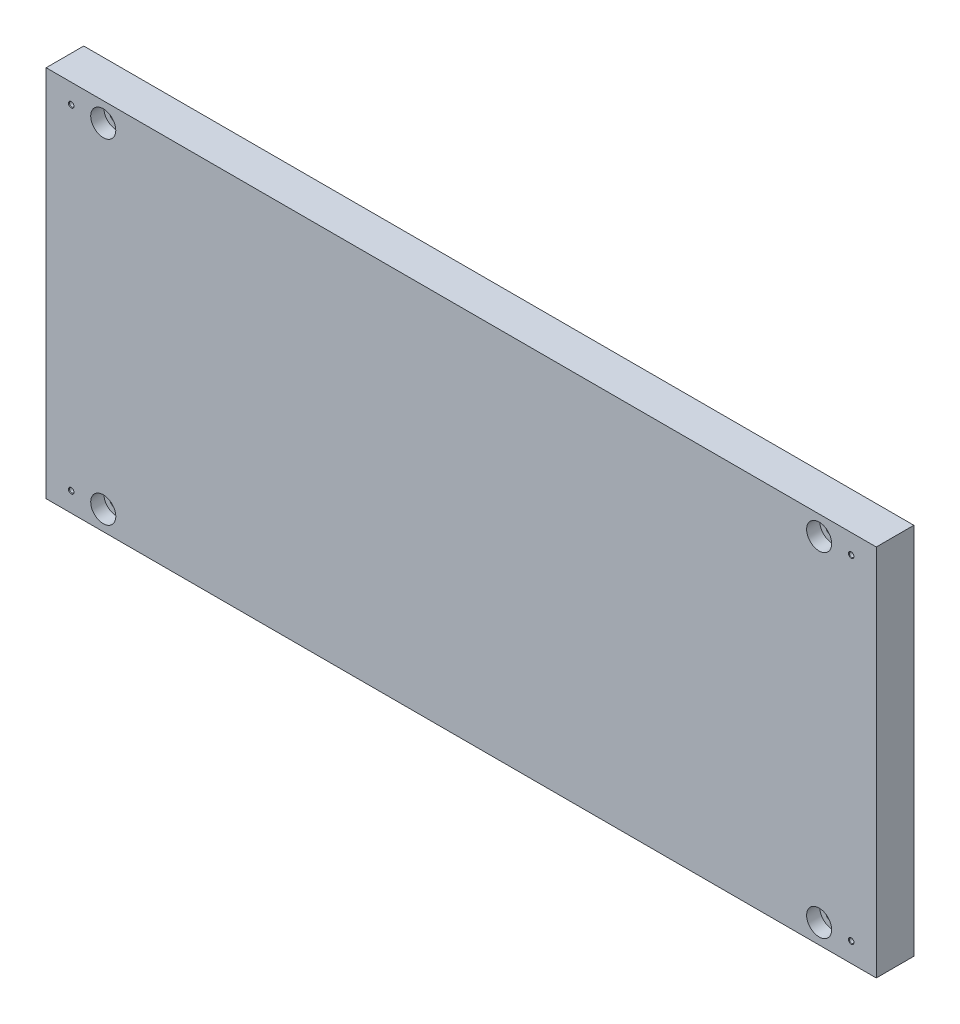
SolidWorks part; units mm, degrees
ref_plane "Płaszczyzna przednia" through (0, 0, 0) normal (0, 0, 1) x (1, 0, 0)
ref_plane "Płaszczyzna górna" through (0, 0, 0) normal (0, 1, 0) x (1, 0, 0)
ref_plane "Płaszczyzna prawa" through (0, 0, 0) normal (1, 0, 0) x (0, 0, -1)
sketch "Szkic1" plane through (0, 0, 0) normal (0, 0, 1) x (1, 0, 0)
  line L0 (-298, -134) -> (298, -134)
  line L1 (298, -134) -> (298, 134)
  line L2 (298, 134) -> (-298, 134)
  line L3 (-298, 134) -> (-298, -134)
extrude "Dodanie-wyciągnięcie1" add sketch "Szkic1" along normal blind 27
ref_plane "Płaszczyzna1" through (257, 0, 0) normal (1, 0, 0) x (0, 0, -1)
sketch "Szkic2" plane through (257, 0, 0) normal (1, 0, 0) x (0, 0, -1)
  line L0 (-17.5, 120) -> (-17.5, 125)
  line L1 (-17.5, 125) -> (0, 125)
  line L2 (0, 125) -> (0, 120)
  line L3 (0, 120) -> (-17.5, 120)
  line L4 (0, 120) -> (-17.5, 120) construction
revolve "Wycięcie-obrót1" cut sketch "Szkic2" angle 360 about L4 reverse direction yes
sketch "Szkic3" plane through (257, 0, 0) normal (1, 0, 0) x (0, 0, -1)
  line L0 (0, -120) -> (0, -125)
  line L1 (0, -125) -> (-17.5, -125)
  line L2 (-17.5, -125) -> (-17.5, -120)
  line L3 (-17.5, -120) -> (0, -120)
  line L4 (-17.5, -120) -> (0, -120) construction
revolve "Wycięcie-obrót2" cut sketch "Szkic3" angle 360 about L4 reverse direction yes
ref_plane "Płaszczyzna2" through (-257, 0, 0) normal (1, 0, 0) x (0, 0, -1)
sketch "Szkic4" plane through (-257, 0, 0) normal (1, 0, 0) x (0, 0, -1)
  line L0 (-17.5, 120) -> (-17.5, 125)
  line L1 (-17.5, 125) -> (0, 125)
  line L2 (0, 125) -> (0, 120)
  line L3 (0, 120) -> (-17.5, 120)
  line L4 (0, 120) -> (-17.5, 120) construction
revolve "Wycięcie-obrót3" cut sketch "Szkic4" angle 360 about L4 reverse direction yes
sketch "Szkic5" plane through (-257, 0, 0) normal (1, 0, 0) x (0, 0, -1)
  line L0 (0, -120) -> (0, -125)
  line L1 (0, -125) -> (-17.5, -125)
  line L2 (-17.5, -125) -> (-17.5, -120)
  line L3 (-17.5, -120) -> (0, -120)
  line L4 (-17.5, -120) -> (0, -120) construction
revolve "Wycięcie-obrót4" cut sketch "Szkic5" angle 360 about L4 reverse direction yes
sketch "Szkic6" plane through (-257, 0, 0) normal (1, 0, 0) x (0, 0, -1)
  line L0 (-27, 120) -> (-27, 129)
  line L1 (-27, 129) -> (-17.5, 129)
  line L2 (-17.5, 129) -> (-17.5, 120)
  line L3 (-17.5, 120) -> (-27, 120)
  line L4 (-17.5, 120) -> (-27, 120) construction
revolve "Wycięcie-obrót5" cut sketch "Szkic6" angle 360 about L4 reverse direction yes
sketch "Szkic7" plane through (257, 0, 0) normal (1, 0, 0) x (0, 0, -1)
  line L0 (-27, 120) -> (-27, 129)
  line L1 (-27, 129) -> (-17.5, 129)
  line L2 (-17.5, 129) -> (-17.5, 120)
  line L3 (-17.5, 120) -> (-27, 120)
  line L4 (-17.5, 120) -> (-27, 120) construction
revolve "Wycięcie-obrót6" cut sketch "Szkic7" angle 360 about L4 reverse direction yes
sketch "Szkic8" plane through (-257, 0, 0) normal (1, 0, 0) x (0, 0, -1)
  line L0 (-17.5, -120) -> (-17.5, -129)
  line L1 (-17.5, -129) -> (-27, -129)
  line L2 (-27, -129) -> (-27, -120)
  line L3 (-27, -120) -> (-17.5, -120)
  line L4 (-27, -120) -> (-17.5, -120) construction
revolve "Wycięcie-obrót7" cut sketch "Szkic8" angle 360 about L4 reverse direction yes
sketch "Szkic9" plane through (257, 0, 0) normal (1, 0, 0) x (0, 0, -1)
  line L0 (-17.5, -120) -> (-17.5, -129)
  line L1 (-17.5, -129) -> (-27, -129)
  line L2 (-27, -129) -> (-27, -120)
  line L3 (-27, -120) -> (-17.5, -120)
  line L4 (-27, -120) -> (-17.5, -120) construction
revolve "Wycięcie-obrót8" cut sketch "Szkic9" angle 360 about L4 reverse direction yes
ref_plane "Płaszczyzna3" through (-280, 0, 0) normal (1, 0, 0) x (0, 0, -1)
sketch "Szkic10" plane through (-280, 0, 0) normal (1, 0, 0) x (0, 0, -1)
  line L0 (-27, 120) -> (-27, 122)
  line L1 (-27, 122) -> (-26.621, 121.621)
  line L2 (-26.621, 121.621) -> (-17.2812, 121.621)
  line L3 (-17.2812, 121.621) -> (-16.3453, 120)
  line L4 (-16.3453, 120) -> (-27, 120)
  line L5 (-16.3453, 120) -> (-27, 120) construction
revolve "Wycięcie-obrót9" cut sketch "Szkic10" angle 360 about L5 reverse direction yes
cosmetic thread "Oznaczenie gwintu1" parameters "D1"=9.5, "D2"=4
sketch "Szkic11" plane through (-280, 0, 0) normal (1, 0, 0) x (0, 0, -1)
  line L0 (-16.3453, -120) -> (-17.2812, -121.621)
  line L1 (-17.2812, -121.621) -> (-26.621, -121.621)
  line L2 (-26.621, -121.621) -> (-27, -122)
  line L3 (-27, -122) -> (-27, -120)
  line L4 (-27, -120) -> (-16.3453, -120)
  line L5 (-27, -120) -> (-16.3453, -120) construction
revolve "Wycięcie-obrót10" cut sketch "Szkic11" angle 360 about L5 reverse direction yes
cosmetic thread "Oznaczenie gwintu2" parameters "D1"=9.5, "D2"=4
ref_plane "Płaszczyzna4" through (280, 0, 0) normal (1, 0, 0) x (0, 0, -1)
sketch "Szkic12" plane through (280, 0, 0) normal (1, 0, 0) x (0, 0, -1)
  line L0 (-27, 120) -> (-27, 122)
  line L1 (-27, 122) -> (-26.621, 121.621)
  line L2 (-26.621, 121.621) -> (-17.2812, 121.621)
  line L3 (-17.2812, 121.621) -> (-16.3453, 120)
  line L4 (-16.3453, 120) -> (-27, 120)
  line L5 (-16.3453, 120) -> (-27, 120) construction
revolve "Wycięcie-obrót11" cut sketch "Szkic12" angle 360 about L5 reverse direction yes
cosmetic thread "Oznaczenie gwintu3" parameters "D1"=9.5, "D2"=4
sketch "Szkic13" plane through (280, 0, 0) normal (1, 0, 0) x (0, 0, -1)
  line L0 (-16.3453, -120) -> (-17.2812, -121.621)
  line L1 (-17.2812, -121.621) -> (-26.621, -121.621)
  line L2 (-26.621, -121.621) -> (-27, -122)
  line L3 (-27, -122) -> (-27, -120)
  line L4 (-27, -120) -> (-16.3453, -120)
  line L5 (-27, -120) -> (-16.3453, -120) construction
revolve "Wycięcie-obrót12" cut sketch "Szkic13" angle 360 about L5 reverse direction yes
cosmetic thread "Oznaczenie gwintu4" parameters "D1"=9.5, "D2"=4
ref_plane "Płaszczyzna5" through (0, 0, 17.5) normal (0, 0, 1) x (1, 0, 0)
ref_plane "Płaszczyzna6" through (0, 0, 27) normal (0, 0, 1) x (1, 0, 0)
ref_plane "IP1 XY" through (0, 0, 0) normal (0, 0, 1) x (1, 0, 0)
ref_plane "IP1 XZ" through (0, 0, 0) normal (0, -1, 0) x (-1, 0, 0)
ref_plane "IP1 YZ" through (0, 0, 0) normal (1, 0, 0) x (0, 0, -1)
ref_axis "IP1 X" through (-80.9, 0, 0) along (1, 0, 0)
ref_axis "IP1 Y" through (0, -50, 0) along (0, 1, 0)
ref_axis "IP1 Z" through (0, 0, 80.9) along (0, 0, -1)
sketch3d "IP1"
  point P0 (0, 0, 0)
ref_plane "IP2 XY" through (0, 0, 17.5) normal (0, 0, 1) x (1, 0, 0)
ref_plane "IP2 XZ" through (0, 120, 0) normal (0, -1, 0) x (-1, 0, 0)
ref_plane "IP2 YZ" through (-257, 0, 0) normal (1, 0, 0) x (0, 0, -1)
ref_axis "IP2 X" through (-80.9, 120, 17.5) along (1, 0, 0)
ref_axis "IP2 Y" through (-257, -50, 17.5) along (0, 1, 0)
ref_axis "IP2 Z" through (-257, 120, 80.9) along (0, 0, -1)
sketch3d "IP2"
  point P0 (-257, 120, 17.5)
ref_plane "IP3 XY" through (0, 0, 17.5) normal (0, 0, 1) x (1, 0, 0)
ref_plane "IP3 XZ" through (0, 120, 0) normal (0, -1, 0) x (-1, 0, 0)
ref_plane "IP3 YZ" through (257, 0, 0) normal (1, 0, 0) x (0, 0, -1)
ref_axis "IP3 X" through (-80.9, 120, 17.5) along (1, 0, 0)
ref_axis "IP3 Y" through (257, -50, 17.5) along (0, 1, 0)
ref_axis "IP3 Z" through (257, 120, 80.9) along (0, 0, -1)
sketch3d "IP3"
  point P0 (257, 120, 17.5)
ref_plane "IP4 XY" through (0, 0, 17.5) normal (0, 0, 1) x (1, 0, 0)
ref_plane "IP4 XZ" through (0, -120, 0) normal (0, -1, 0) x (-1, 0, 0)
ref_plane "IP4 YZ" through (257, 0, 0) normal (1, 0, 0) x (0, 0, -1)
ref_axis "IP4 X" through (-80.9, -120, 17.5) along (1, 0, 0)
ref_axis "IP4 Y" through (257, -50, 17.5) along (0, 1, 0)
ref_axis "IP4 Z" through (257, -120, 80.9) along (0, 0, -1)
sketch3d "IP4"
  point P0 (257, -120, 17.5)
ref_plane "IP5 XY" through (0, 0, 17.5) normal (0, 0, 1) x (1, 0, 0)
ref_plane "IP5 XZ" through (0, -120, 0) normal (0, -1, 0) x (-1, 0, 0)
ref_plane "IP5 YZ" through (-257, 0, 0) normal (1, 0, 0) x (0, 0, -1)
ref_axis "IP5 X" through (-80.9, -120, 17.5) along (1, 0, 0)
ref_axis "IP5 Y" through (-257, -50, 17.5) along (0, 1, 0)
ref_axis "IP5 Z" through (-257, -120, 80.9) along (0, 0, -1)
sketch3d "IP5"
  point P0 (-257, -120, 17.5)
ref_plane "IP6 XY" through (0, 0, 27) normal (0, 0, 1) x (1, 0, 0)
ref_plane "IP6 XZ" through (0, 120, 0) normal (0, -1, 0) x (-1, 0, 0)
ref_plane "IP6 YZ" through (-280, 0, 0) normal (1, 0, 0) x (0, 0, -1)
ref_axis "IP6 X" through (-80.9, 120, 27) along (1, 0, 0)
ref_axis "IP6 Y" through (-280, -50, 27) along (0, 1, 0)
ref_axis "IP6 Z" through (-280, 120, 80.9) along (0, 0, -1)
sketch3d "IP6"
  point P0 (-280, 120, 27)
ref_plane "IP7 XY" through (0, 0, 27) normal (0, 0, 1) x (1, 0, 0)
ref_plane "IP7 XZ" through (0, 120, 0) normal (0, -1, 0) x (-1, 0, 0)
ref_plane "IP7 YZ" through (280, 0, 0) normal (1, 0, 0) x (0, 0, -1)
ref_axis "IP7 X" through (-80.9, 120, 27) along (1, 0, 0)
ref_axis "IP7 Y" through (280, -50, 27) along (0, 1, 0)
ref_axis "IP7 Z" through (280, 120, 80.9) along (0, 0, -1)
sketch3d "IP7"
  point P0 (280, 120, 27)
ref_plane "IP8 XY" through (0, 0, 27) normal (0, 0, 1) x (1, 0, 0)
ref_plane "IP8 XZ" through (0, -120, 0) normal (0, -1, 0) x (-1, 0, 0)
ref_plane "IP8 YZ" through (280, 0, 0) normal (1, 0, 0) x (0, 0, -1)
ref_axis "IP8 X" through (-80.9, -120, 27) along (1, 0, 0)
ref_axis "IP8 Y" through (280, -50, 27) along (0, 1, 0)
ref_axis "IP8 Z" through (280, -120, 80.9) along (0, 0, -1)
sketch3d "IP8"
  point P0 (280, -120, 27)
ref_plane "IP9 XY" through (0, 0, 27) normal (0, 0, 1) x (1, 0, 0)
ref_plane "IP9 XZ" through (0, -120, 0) normal (0, -1, 0) x (-1, 0, 0)
ref_plane "IP9 YZ" through (-280, 0, 0) normal (1, 0, 0) x (0, 0, -1)
ref_axis "IP9 X" through (-80.9, -120, 27) along (1, 0, 0)
ref_axis "IP9 Y" through (-280, -50, 27) along (0, 1, 0)
ref_axis "IP9 Z" through (-280, -120, 80.9) along (0, 0, -1)
sketch3d "IP9"
  point P0 (-280, -120, 27)
